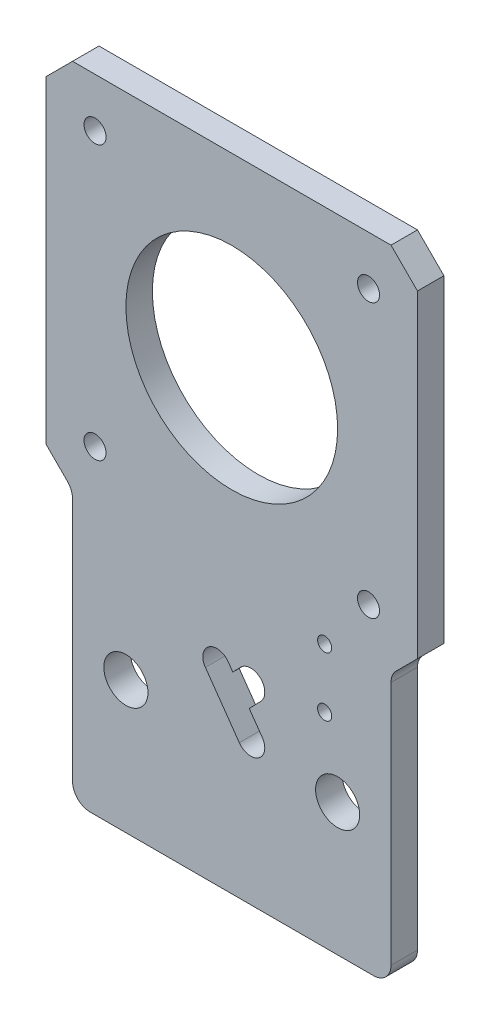
SolidWorks part; units mm, degrees
ref_plane "Plano frontal" through (0, 0, 0) normal (0, 0, 1) x (1, 0, 0)
ref_plane "Plano superior" through (0, 0, 0) normal (0, 1, 0) x (1, 0, 0)
ref_plane "Plano direito" through (0, 0, 0) normal (1, 0, 0) x (0, 0, -1)
sketch "Sketch1" plane through (0, 0, 0) normal (0, 0, 1) x (1, 0, 0)
  line L1 (-18.05, -21.05) -> (18.05, -21.05) construction
  line L2 (18.05, -51.655) -> (18.05, -21.05)
  line L4 (-18.05, -51.655) -> (-18.05, -21.05)
  line L5 (18.05, -51.655) -> (-18.05, -51.655)
  line L16 (-21.05, -18.05) -> (-18.05, -21.05)
  line L18 (18.05, -21.05) -> (21.05, -18.05)
  line L19 (21.05, -18.05) -> (21.05, 18.05)
  line L20 (21.05, 18.05) -> (18.05, 21.05)
  line L21 (18.05, 21.05) -> (-18.05, 21.05)
  line L22 (-18.05, 21.05) -> (-21.05, 18.05)
  line L23 (-21.05, 18.05) -> (-21.05, -18.05)
  circle A3 centre (0, 0) radius 12
  dimension "D2" = 36.1
  dimension "D3" = 4.2426
  dimension "D1" = 30.605
extrude "Boss-Extrude1" add sketch "Sketch1" along normal blind 3
hole_wizard "Tap Drill for M3 Tap1" positions "Sketch3" profile "Sketch2" hole size "M3" standard "ISO"
sketch "Sketch3" plane through (0, 0, 3) normal (0, 0, 1) x (1, 0, 0)
  point P0 (-15.5, 15.5)
  point P3 (15.5, 15.5)
  point P6 (-15.5, -15.5)
  point P9 (15.5, -15.5)
sketch "Sketch2" plane through (-15.5, 15.5, 3) normal (1, 0, 0) x (0, -1, 0)
  line L0 (0, 0) -> (0, 5.7511)
  line L1 (0, 5.7511) -> (1.25, 5)
  line L2 (1.25, 5) -> (1.25, 0)
  line L5 (1.25, 0) -> (0, 0)
  line L10 (0, 5.7511) -> (-1.25, 5) construction
  line L11 (0, -6.35) -> (0, 107.95) construction
  dimension "Hole Dia." = 2.5
  dimension "Hole Depth" = 5
  dimension "Drill Angle" = 118
hole_wizard "Tap Drill for M6 Tap1" positions "Sketch5" profile "Sketch4" hole size "M6" standard "ISO"
sketch "Sketch5" plane through (0, 0, 3) normal (0, 0, 1) x (1, 0, 0)
  line L1 (0, -51.655) -> (0, -21.05) construction
  line L2 (-18.05, -51.655) -> (18.05, -51.655) construction
  line L4 (-579.95, -36.655) -> (23.05, -36.655) construction
  point P28 (12, -36.655)
  point P32 (-12, -36.655)
  point P35 (0, 0)
  point P36 (0, 0)
sketch "Sketch4" plane through (-12, -36.655, 3) normal (1, 0, 0) x (0, -1, 0)
  line L0 (0, 0) -> (0, 6.5022)
  line L1 (0, 6.5022) -> (2.5, 5)
  line L2 (2.5, 5) -> (2.5, 0)
  line L5 (2.5, 0) -> (0, 0)
  line L10 (0, 6.5022) -> (-2.5, 5) construction
  line L11 (0, -6.35) -> (0, 107.95) construction
  dimension "Hole Dia." = 5
  dimension "Hole Depth" = 5
  dimension "Drill Angle" = 118
fillet "Fillet1" radius 2 4 edges at (18.05, -21.05, 1.5) (18.05, -51.655, 1.5) (-18.05, -51.655, 1.5) (-18.05, -21.05, 1.5)
hole_wizard "Tap Drill for M2 Tap1" positions "Sketch7" profile "Sketch6" hole size "M2" standard "ISO"
sketch "Sketch7" plane through (0, 0, 3) normal (0, 0, 1) x (1, 0, 0)
  point P0 (10.5295, -21.8613)
  point P3 (10.5295, -28.5613)
sketch "Sketch6" plane through (10.5295, -21.8613, 3) normal (1, 0, 0) x (0, -1, 0)
  line L0 (0, 0) -> (0, 5.4807)
  line L1 (0, 5.4807) -> (0.8, 5)
  line L2 (0.8, 5) -> (0.8, 0)
  line L5 (0.8, 0) -> (0, 0)
  line L10 (0, 5.4807) -> (-0.8, 5) construction
  line L11 (0, -6.35) -> (0, 107.95) construction
  dimension "Hole Dia." = 1.6
  dimension "Hole Depth" = 5
  dimension "Drill Angle" = 118
sketch "Sketch8" plane through (0, 0, 0) normal (0, 0, -1) x (-1, 0, 0)
  line L0 (8.6131, -51.655) -> (-8.6131, -51.655) construction
  line L1 (0, -51.655) -> (0, -33.8118) construction
  line L2 (2.9921, -30.9145) -> (-0.8553, -36.3863)
  line L3 (0.3948, -29.0883) -> (-0.1195, -29.8197)
  line L4 (-1.0138, -28.8967) -> (0, -29.943)
  line L5 (-3.294, -31.1061) -> (-1.9785, -32.4637)
  line L6 (-1.9785, -32.4637) -> (-3.4525, -34.5601)
  line L7 (0, -29.943) -> (0, -16.4461) construction
  arc A0 (2.9921, -30.9145) -> (0.3948, -29.0883) centre (1.6934, -30.0014) ccw
  arc A1 (-3.4525, -34.5601) -> (-0.8553, -36.3863) centre (-2.1539, -35.4732) ccw
  arc A2 (-1.0138, -28.8967) -> (-3.294, -31.1061) centre (-2.1539, -30.0014) ccw
  point P8 (-0.2302, -32.7373)
  point P13 (-1.077, -31.1128)
extrude "Cut-Extrude1" cut sketch "Sketch8" against normal blind 10 contours L4 A2 L5 L6 A1 L2 A0 L3 region at (0.6683, -32.1273, 0)
